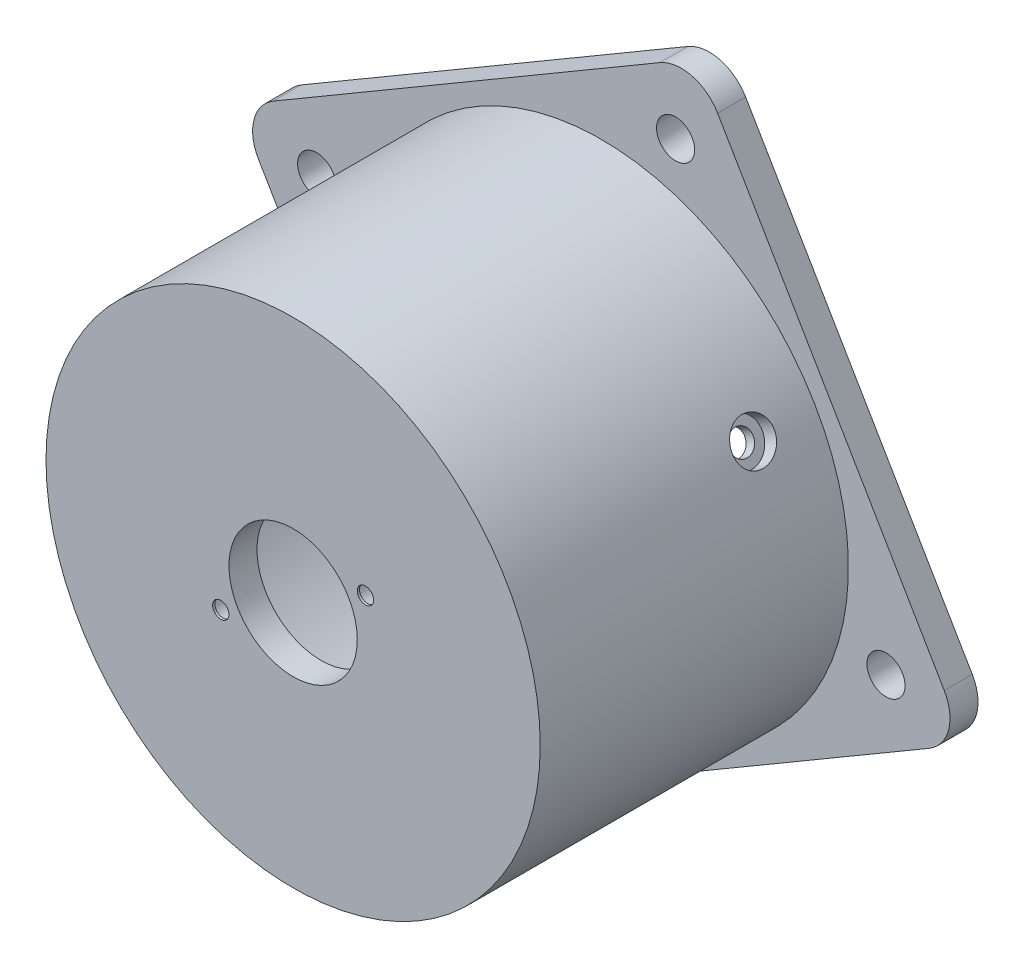
SolidWorks part; units mm, degrees
material "Acrylic (Medium-high impact)"
ref_plane "Front Plane" through (0, 0, 0) normal (0, 0, 1) x (1, 0, 0)
ref_plane "Top Plane" through (0, 0, 0) normal (0, 1, 0) x (1, 0, 0)
ref_plane "Right Plane" through (0, 0, 0) normal (1, 0, 0) x (0, 0, -1)
sketch "Sketch1" plane through (0, 0, 0) normal (0, 0, 1) x (1, 0, 0)
  circle A0 centre (0, 0) radius 25.3365
  circle A1 centre (0, 0) radius 28.0035
  dimension "D1" = 50.673
extrude "Boss-Extrude1" add sketch "Sketch1" along normal blind 38.1
sketch "Sketch10" plane through (0, 0, 38.1) normal (0, 0, 1) x (1, 0, 0)
  circle A0 centre (0, 0) radius 28.0035
  circle A1 centre (0, 0) radius 28.0035 construction
extrude "Boss-Extrude2" add sketch "Sketch10" against normal blind 3.175
ref_plane "Plane1" through (0, 0, 10.2108) normal (0, 0, -1) x (-1, 0, 0)
sketch "Sketch11" plane through (0, 0, 10.2108) normal (0, 0, -1) x (-1, 0, 0)
  line L0 (0, 0) -> (0, -28.0035) construction
  line L1 (0, 0) -> (-24.2517, 14.0018) construction
  line L2 (0, 0) -> (24.2517, 14.0018) construction
  circle A0 centre (0, 0) radius 28.0035 construction
  dimension "D1" = 120
ref_plane "Plane2" through (-24.2517, 14.0018, 10.2108) normal (-0.866, 0.5, 0) x (0, 0, -1)
ref_plane "Plane3" through (24.2517, 14.0018, 10.2108) normal (0.866, 0.5, 0) x (0, 0, 1)
ref_plane "Plane4" through (0, -28.0035, 10.2108) normal (0, -1, 0) x (-1, 0, 0)
hole_wizard "CBORE for #2 Pan Head Machine Screw1" positions "Sketch15" profile "Sketch14" counterbore size "#2" standard "ANSI Inch" end condition up to next
sketch "Sketch15" plane through (-24.2517, 14.0018, 10.2108) normal (-0.866, 0.5, 0) x (0, 0, -1)
  point P0 (0, 0)
sketch "Sketch14" plane through (-24.2517, 14.0018, 10.2108) normal (0, 0, 1) x (-0.5, -0.866, 0)
  line L0 (0, 0) -> (0, 2.667)
  line L1 (0, 2.667) -> (1.3526, 2.667)
  line L3 (1.3526, 2.667) -> (1.3525, 1.5748)
  line L4 (1.3525, 1.5748) -> (2.3812, 1.5748)
  line L5 (2.3812, 1.5748) -> (2.3812, 0)
  line L7 (2.3812, 0) -> (0, 0)
  line L11 (0, -6.35) -> (0, 107.95) construction
  dimension "Thru Hole Dia." = 2.7051
  dimension "Thru Hole Depth" = 2.667
  dimension "C'Bore Dia." = 4.7625
  dimension "C'Bore Depth" = 1.5748
hole_wizard "CBORE for #2 Pan Head Machine Screw2" positions "Sketch17" profile "Sketch16" counterbore size "#2" standard "ANSI Inch" end condition up to next
sketch "Sketch17" plane through (24.2517, 14.0018, 10.2108) normal (0.866, 0.5, 0) x (0, 0, 1)
  point P0 (0, 0)
sketch "Sketch16" plane through (24.2517, 14.0018, 10.2108) normal (0, 0, 1) x (-0.5, 0.866, 0)
  line L0 (0, 0) -> (0, 2.667)
  line L1 (0, 2.667) -> (1.3526, 2.667)
  line L3 (1.3526, 2.667) -> (1.3526, 1.5748)
  line L4 (1.3526, 1.5748) -> (2.3812, 1.5748)
  line L5 (2.3812, 1.5748) -> (2.3812, 0)
  line L7 (2.3812, 0) -> (0, 0)
  line L11 (0, -6.35) -> (0, 107.95) construction
  dimension "Thru Hole Dia." = 2.7051
  dimension "Thru Hole Depth" = 2.667
  dimension "C'Bore Dia." = 4.7625
  dimension "C'Bore Depth" = 1.5748
hole_wizard "CBORE for #2 Pan Head Machine Screw3" positions "Sketch19" profile "Sketch18" counterbore size "#2" standard "ANSI Inch" end condition up to next
sketch "Sketch19" plane through (0, -28.0035, 10.2108) normal (0, -1, 0) x (-1, 0, 0)
  point P0 (0, 0)
sketch "Sketch18" plane through (0, -28.0035, 10.2108) normal (1, 0, 0) x (0, 0, -1)
  line L0 (0, 0) -> (0, 2.667)
  line L1 (0, 2.667) -> (1.3526, 2.667)
  line L3 (1.3526, 2.667) -> (1.3526, 1.5748)
  line L4 (1.3526, 1.5748) -> (2.3812, 1.5748)
  line L5 (2.3812, 1.5748) -> (2.3812, 0)
  line L7 (2.3812, 0) -> (0, 0)
  line L11 (0, -6.35) -> (0, 107.95) construction
  dimension "Thru Hole Dia." = 2.7051
  dimension "Thru Hole Depth" = 2.667
  dimension "C'Bore Dia." = 4.7625
  dimension "C'Bore Depth" = 1.5748
sketch "Sketch20" plane through (0, 0, 38.1) normal (0, 0, 1) x (1, 0, 0)
  circle A0 centre (0, 0) radius 7.27
  circle A1 centre (0, 0) radius 6 construction
  dimension "D1" = 1.27
extrude "Cut-Extrude1" cut sketch "Sketch20" against normal up to next
hole_wizard "Hole1" positions "Sketch21" profile "Sketch22" legacy
sketch "Sketch21" plane through (0, 0, 34.925) normal (0, 0, -1) x (-1, 0, 0)
  point P0 (-8.1957, 4.8042)
  point P3 (8.1957, -4.8042)
sketch "Sketch22" plane through (8.1957, 4.8042, 34.925) normal (1, 0, 0) x (0, 1, 0)
  line L0 (0, 0) -> (0, 2.921)
  line L1 (0, 2.921) -> (1.4986, 2.921)
  line L2 (1.4986, 2.921) -> (1.6383, 0)
  line L3 (1.6383, 0) -> (0, 0)
  line L4 (0, 110) -> (0, -10) construction
  dimension "Minor Diameter" = 2.9972
  dimension "Depth" = 2.921
  dimension "Major Diameter" = 3.2766
hole_wizard "#0 Clearance Hole1" positions "Sketch23" profile "Sketch24" hole size "#0" standard "ANSI Inch" end condition up to next
sketch "Sketch23" plane through (0, 0, 34.925) normal (0, 0, -1) x (-1, 0, 0)
  point P0 (-8.1957, 4.8042)
  point P3 (8.1957, -4.8042)
sketch "Sketch24" plane through (8.1957, 4.8042, 34.925) normal (1, 0, 0) x (0, 1, 0)
  line L0 (0, 0) -> (0, 3.175)
  line L1 (0, 3.175) -> (0.9271, 3.175)
  line L2 (0.9271, 3.175) -> (0.9271, 0)
  line L5 (0.9271, 0) -> (0, 0)
  line L11 (0, -6.35) -> (0, 107.95) construction
  dimension "Thru Hole Dia." = 1.8542
  dimension "Thru Hole Depth" = 3.175
chamfer "Chamfer1" distance 1.27 angle 45 1 edges at (25.3365, 0, 0)
sketch "Sketch25" plane through (0, 0, 0) normal (0, 0, -1) x (-1, 0, 0)
  line L0 (37.1551, 13.1831) -> (-6.6486, 38.8598)
  line L1 (38.8598, 6.6486) -> (13.1831, -37.1551)
  line L2 (6.6486, -38.8598) -> (-37.1551, -13.1831)
  line L3 (-13.1831, 37.1551) -> (-38.8598, -6.6486)
  arc A0 (-38.8598, -6.6486) -> (-37.1551, -13.1831) centre (-34.7402, -9.0635) ccw
  arc A1 (6.6486, -38.8598) -> (13.1831, -37.1551) centre (9.0635, -34.7402) ccw
  arc A2 (38.8598, 6.6486) -> (37.1551, 13.1831) centre (34.7402, 9.0635) ccw
  arc A3 (-6.6486, 38.8598) -> (-13.1831, 37.1551) centre (-9.0635, 34.7402) ccw
  circle A4 centre (-8.4158, 32.2578) radius 2.159
  circle A5 centre (32.2578, 8.4158) radius 2.159
  circle A6 centre (8.4158, -32.2578) radius 2.159
  circle A7 centre (-32.2578, -8.4158) radius 2.159
extrude "Boss-Extrude3" add sketch "Sketch25" against normal blind 3.175
sketch "Sketch26" plane through (0, 0, 3.175) normal (0, 0, 1) x (1, 0, 0)
  circle A1 centre (0, 0) radius 25.3365
  circle A2 centre (0, 0) radius 25.3365
  dimension "D1" = 0
extrude "Cut-Extrude2" cut sketch "Sketch26" against normal through all
